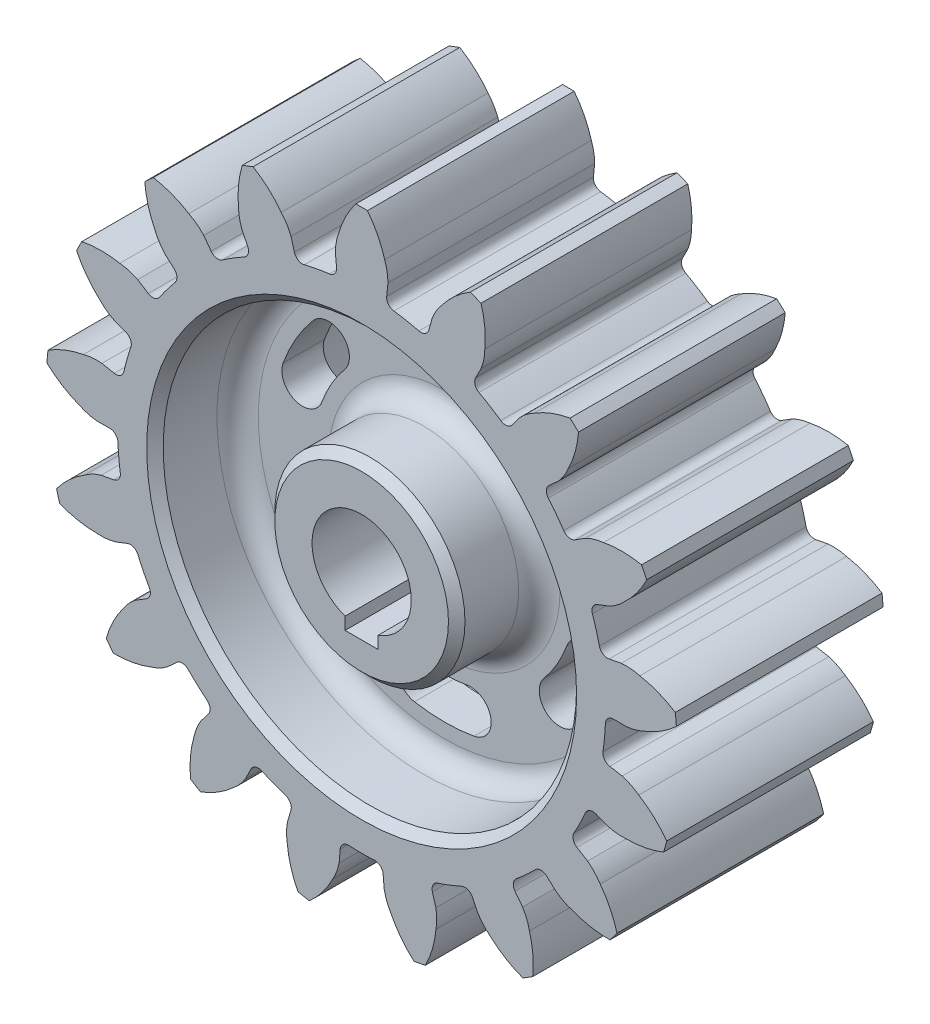
SolidWorks part; units mm, degrees
material "AISI 1020"
ref_plane "Plano frontal" through (0, 0, 0) normal (0, 0, 1) x (1, 0, 0)
ref_plane "Plano superior" through (0, 0, 0) normal (0, 1, 0) x (1, 0, 0)
ref_plane "Plano direito" through (0, 0, 0) normal (1, 0, 0) x (0, 0, -1)
sketch "Esboço1" plane through (0, 0, 0) normal (0, 0, 1) x (1, 0, 0)
  line L0 (0, -809.6366) -> (0, 39672.1915) construction
  line L1 (-4, -11.3137) -> (-4, -14.3137)
  line L2 (-4, -14.3137) -> (4, -14.3137)
  line L3 (4, -14.3137) -> (4, -11.3137)
  line L4 (-6.36, 63.6832) -> (-5.8631, 58.708)
  line L5 (6.36, 63.6832) -> (5.8631, 58.708)
  arc A0 (4, -11.3137) -> (-4, -11.3137) centre (0, 0) ccw
  circle A1 centre (0, 0) radius 23
  circle A2 centre (0, 0) radius 36.5 construction
  circle A3 centre (0, 0) radius 59
  circle A4 centre (0, 0) radius 64 construction
  circle A5 centre (0, 0) radius 68.34 construction
  arc A6 (1.404, 76.3271) -> (-1.404, 76.3271) centre (0, 0) ccw
  circle A7 centre (0, 0) radius 50
  arc A8 (-6.3382, 35.9455) -> (6.3382, 35.9455) centre (0, 0) cw construction
  arc A13 (7.2064, 40.8695) -> (-7.2064, 40.8695) centre (0, 0) ccw
  arc A14 (5.4699, 31.0214) -> (-5.4699, 31.0214) centre (0, 0) ccw
  arc A15 (5.4699, 31.0214) -> (7.2064, 40.8695) centre (6.3382, 35.9455) ccw
  arc A16 (-7.2064, 40.8695) -> (-5.4699, 31.0214) centre (-6.3382, 35.9455) ccw
  arc A17 (29.6003, 10.7736) -> (24.1304, 20.2478) centre (0, 0) ccw
  arc A18 (29.6003, 10.7736) -> (38.9972, 14.1938) centre (34.2988, 12.4837) ccw
  arc A19 (31.7908, 26.6757) -> (24.1304, 20.2478) centre (27.9606, 23.4617) ccw
  arc A20 (38.9972, 14.1938) -> (31.7908, 26.6757) centre (0, 0) ccw
  arc A21 (27.9606, 23.4617) -> (34.2988, 12.4837) centre (0, 0) cw construction
  arc A22 (24.1304, -20.2478) -> (29.6003, -10.7736) centre (0, 0) ccw
  arc A23 (24.1304, -20.2478) -> (31.7908, -26.6757) centre (27.9606, -23.4617) ccw
  arc A24 (38.9972, -14.1938) -> (29.6003, -10.7736) centre (34.2988, -12.4837) ccw
  arc A25 (31.7908, -26.6757) -> (38.9972, -14.1938) centre (0, 0) ccw
  arc A26 (34.2988, -12.4837) -> (27.9606, -23.4617) centre (0, 0) cw construction
  arc A27 (-5.4699, -31.0214) -> (5.4699, -31.0214) centre (0, 0) ccw
  arc A28 (-5.4699, -31.0214) -> (-7.2064, -40.8695) centre (-6.3382, -35.9455) ccw
  arc A29 (7.2064, -40.8695) -> (5.4699, -31.0214) centre (6.3382, -35.9455) ccw
  arc A30 (-7.2064, -40.8695) -> (7.2064, -40.8695) centre (0, 0) ccw
  arc A31 (6.3382, -35.9455) -> (-6.3382, -35.9455) centre (0, 0) cw construction
  arc A32 (-29.6003, -10.7736) -> (-24.1304, -20.2478) centre (0, 0) ccw
  arc A33 (-29.6003, -10.7736) -> (-38.9972, -14.1938) centre (-34.2988, -12.4837) ccw
  arc A34 (-31.7908, -26.6757) -> (-24.1304, -20.2478) centre (-27.9606, -23.4617) ccw
  arc A35 (-38.9972, -14.1938) -> (-31.7908, -26.6757) centre (0, 0) ccw
  arc A36 (-27.9606, -23.4617) -> (-34.2988, -12.4837) centre (0, 0) cw construction
  arc A37 (-24.1304, 20.2478) -> (-29.6003, 10.7736) centre (0, 0) ccw
  arc A38 (-24.1304, 20.2478) -> (-31.7908, 26.6757) centre (-27.9606, 23.4617) ccw
  arc A39 (-38.9972, 14.1938) -> (-29.6003, 10.7736) centre (-34.2988, 12.4837) ccw
  arc A40 (-31.7908, 26.6757) -> (-38.9972, 14.1938) centre (0, 0) ccw
  arc A41 (-34.2988, 12.4837) -> (-27.9606, 23.4617) centre (0, 0) cw construction
  arc A42 (-6.36, 63.6832) -> (-5.5612, 68.1134) centre (6.28, 63.6911) cw
  arc A43 (-5.5612, 68.1134) -> (-1.404, 76.3271) centre (17.6788, 61.5098) cw
  arc A44 (6.36, 63.6832) -> (5.5612, 68.1134) centre (-6.28, 63.6911) ccw
  arc A45 (5.5612, 68.1134) -> (1.404, 76.3271) centre (-17.6788, 61.5098) ccw
  point P15 (0, -14.3137)
  point P17 (0, 12)
  point P19 (0, 36.5)
  point P28 (31.6099, 18.25)
  point P35 (31.6099, -18.25)
  point P42 (0, -36.5)
  point P49 (-31.6099, -18.25)
  point P56 (-31.6099, 18.25)
  point P61 (0, 0)
  dimension "D1" = 24
  dimension "D2" = 46
  dimension "D3" = 73
  dimension "D4" = 118
  dimension "D5" = 128
  dimension "D6" = 136.68
  dimension "D7" = 152.68
  dimension "D8" = 100
  dimension "D10" = 3
  dimension "D11" = 10
  dimension "D13" = 6
  dimension "D14" = 12.64
  dimension "D15" = 24.16
  dimension "D16" = 12.56
  dimension "D9" = 8
  dimension "D12" = 20
extrude "Ressalto-extrusão1" add sketch "Esboço1" along normal mid plane 50 contours A3 A7 | A1 A0 L3 L2 L1 region at (0, 57.3312, 0) region at (-22.3495, 0, 0)
extrude "Ressalto-extrusão2" add sketch "Esboço1<3>" along normal mid plane 10 contours A7 A40 A38 A37 A39 A35 A33 A32 A34 A30 A28 A27 A29 A25 A23 A22 A24 A20 A18 A17 A19 A16 A13 A15 A14 A1 region at (-48.5858, 0, 0)
sketch "Esboço1<3>" plane through (0, 0, 0) normal (0, 0, 1) x (1, 0, 0) same geometry as "Esboço1"
extrude "Ressalto-extrusão3" add sketch "Esboço1<4>" along normal mid plane 50 contours A44 A45 A6 A43 A42 L4 A3 L5 region at (0, 66.3528, 0)
sketch "Esboço1<4>" plane through (0, 0, 0) normal (0, 0, 1) x (1, 0, 0) same geometry as "Esboço1"
fillet "Filete1" radius 2 2 edges at (5.8631, 58.708, 0) (-5.8631, 58.708, 0)
pattern_circular "PadrãoCircular1" count 17 over 360 about axis through (0, 0, 25) along (0, 0, 1) of "Ressalto-extrusão3", "Filete1"
chamfer "Chanfro2" distance 2 4 edges at (23, 0, 25) (50, 0, 25) (23, 0, -25) (50, 0, -25)
fillet "Filete2" radius 5 4 edges at (50, 0, 5) (50, 0, -5) (23, 0, 5) (23, 0, -5)
